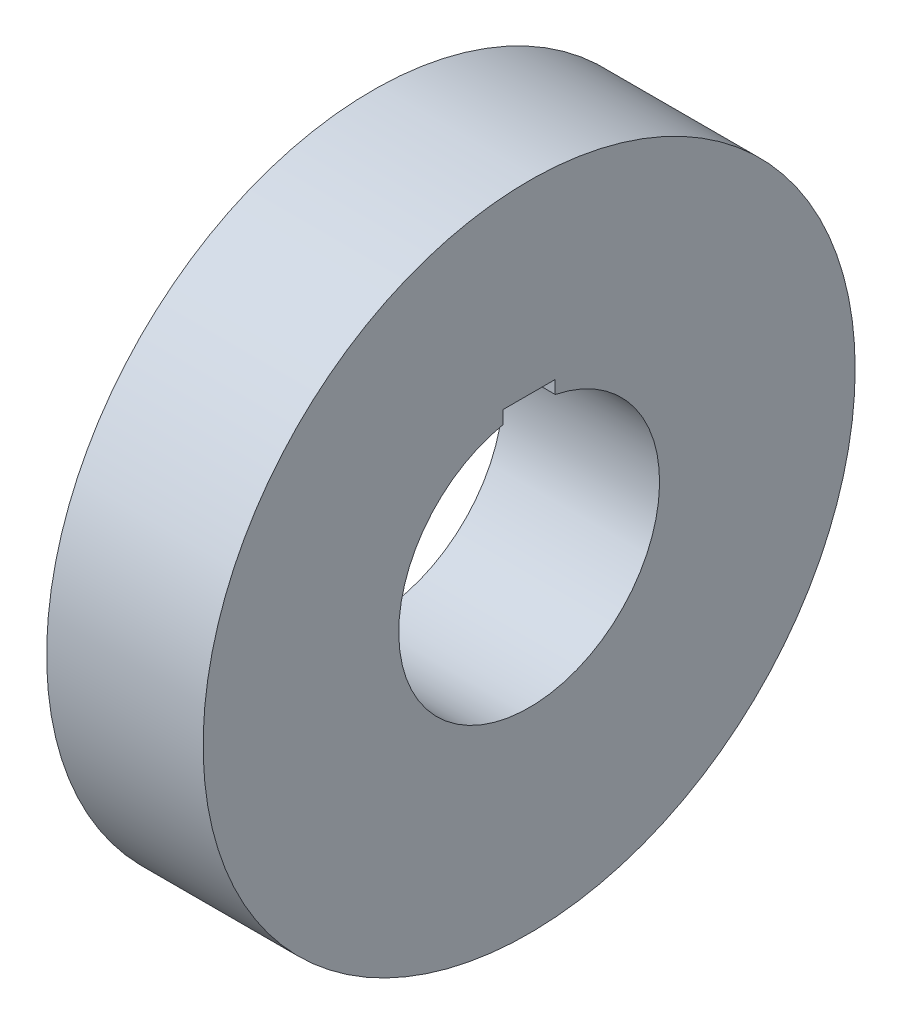
SolidWorks part; units mm, degrees
material "2024-T4"
ref_plane "Front Plane" through (0, 0, 0) normal (0, 0, 1) x (1, 0, 0)
ref_plane "Top Plane" through (0, 0, 0) normal (0, 1, 0) x (1, 0, 0)
ref_plane "Right Plane" through (0, 0, 0) normal (1, 0, 0) x (0, 0, -1)
sketch "Sketch1" plane through (0, 0, 0) normal (1, 0, 0) x (0, 0, -1)
  circle A0 centre (0, 0) radius 25
  circle A1 centre (0, 0) radius 10
  dimension "D1" = 50
  dimension "D2" = 20
extrude "Boss-Extrude1" add sketch "Sketch1" along normal blind 12
sketch "Sketch2" plane through (12, 0, 0) normal (1, 0, 0) x (0, 0, -1)
  line L0 (0, 0) -> (0, 20.3997) construction
  line L1 (2, 10.798) -> (-2, 10.798)
  line L2 (-2, 10.798) -> (-2, 9.798)
  line L3 (2, 10.798) -> (2, 9.798)
  circle A0 centre (0, 0) radius 10 construction
  circle A1 centre (0, 0) radius 10
  point P9 (0, 10.798)
  circle M6 centre (0, 0) radius 10
  dimension "D1" = 4
  dimension "D2" = 1
extrude "Cut-Extrude1" cut sketch "Sketch2" against normal through all contours L0 L1 L2 M6 | L0 A1 L3 L1 region at (12, 10.3634, 1.0388) region at (12, 10.3634, -1.0388)
equation "\"shaft-diameter\" =20mm"
equation "\"D2@Sketch1\"=\"shaft-diameter\""
